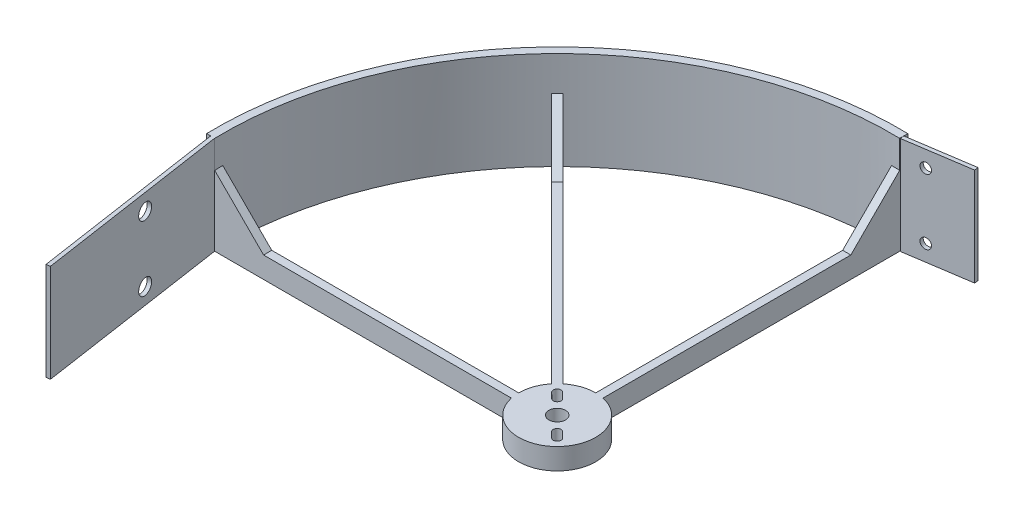
SolidWorks part; units mm, degrees
material "ABS"
ref_plane "Front Plane" through (0, 0, 0) normal (0, 0, 1) x (1, 0, 0)
ref_plane "Top Plane" through (0, 0, 0) normal (0, 1, 0) x (1, 0, 0)
ref_plane "Right Plane" through (0, 0, 0) normal (1, 0, 0) x (0, 0, -1)
sketch "Sketch1" plane through (0, 0, 0) normal (0, 1, 0) x (1, 0, 0)
  line L0 (0, 130.175) -> (0, 9.3426)
  line L1 (3.175, 9.3426) -> (3.175, 130.1363)
  line L2 (0, 0) -> (-22.0351, 22.0351) construction
  line L3 (-22.0351, 22.0351) -> (23.6345, -23.6345) construction
  line L4 (-9.3426, -3.175) -> (-130.1363, -3.175)
  line L5 (-130.175, 0) -> (-9.3426, 0)
  line L6 (3.175, 9.3426) -> (3.175, 130.1363)
  line L7 (3.175, 130.1363) -> (3.175, 133.3122)
  line L8 (-130.1363, -3.175) -> (-133.3122, -3.175)
  line L9 (-93.1633, 90.9182) -> (-10.2883, 8.0432)
  line L10 (-90.9182, 93.1633) -> (-7.1863, 9.4313)
  line L11 (0, 0) -> (-130.175, 0)
  line L12 (-130.175, 0) -> (-129.9364, 0.0546) construction
  line L13 (0, 0) -> (0, 146.05) construction
  circle A0 centre (0, 0) radius 15
  arc A1 (3.175, 130.1363) -> (-130.1363, -3.175) centre (0, 0) ccw
  arc A2 (3.175, 133.3122) -> (-133.3122, -3.175) centre (0, 0) ccw
  point P22 (0, 0)
  dimension "D1" = 30
  dimension "D2" = 133.35
  dimension "D4" = 3.175
  dimension "D3" = 3.175
  dimension "D6" = 1.5875
  dimension "D5" = 1.5875
extrude "Boss-Extrude2" add sketch "Sketch1" along normal blind 8.255 contours A0
extrude "Boss-Extrude3" add sketch "Sketch1<6>" along normal blind 8.255 contours L5 A1 L4 A0 | L6 A1 L0 A0 | A1 A0 region at (1.5882, 0, -72.5246) region at (-51.3161, 0, -51.3161) region at (-72.5246, 0, 1.5882)
sketch "Sketch1<6>" plane through (0, 0, 0) normal (0, 1, 0) x (1, 0, 0) same geometry as "Sketch1"
extrude "Boss-Extrude4" add sketch "Sketch1<7>" along normal blind 38.1 contours L7 A2 L8 A1 region at (-49.8095, 0, -122.3558)
sketch "Sketch1<7>" plane through (0, 0, 0) normal (0, 1, 0) x (1, 0, 0) same geometry as "Sketch1"
ref_plane "Plane1" through (-63.4806, 0, -63.4806) normal (0.7071, 0, 0.7071) x (0.7071, 0, -0.7071)
sketch "Sketch5" plane through (0, 8.255, 0) normal (0, 1, 0) x (1, 0, 0)
  line L0 (0, 0) -> (29.635, 0) construction
  line L1 (0, 0) -> (0, 21.5427) construction
  line L2 (0, 130.175) -> (0, 15) construction
  line L3 (0, 0) -> (29.1655, -1.7838) construction
  line L4 (21.3209, -1.304) -> (-27.7157, 1.6952) construction
  line L5 (0, 0) -> (1.3244, 21.6543) construction
  line L6 (0, 8) -> (0, 0) construction
  line L7 (0, 0) -> (37.8993, -60.1598) construction
  line L8 (0, 0) -> (-19.6346, 0) construction
  line L9 (-130.175, 0) -> (-15, 0) construction
  circle A6 centre (0, 0) radius 3.25
  point P18 (0, 0)
  dimension "D8" = 6.5
  dimension "D2" = 8
  dimension "D5" = 93.5
  dimension "D9" = 90
  dimension "D4" = 57.79
extrude "Cut-Extrude3" cut sketch "Sketch5" against normal blind 63.5
sketch "Sketch6" plane through (0, 0, 3.175) normal (0, 0, 1) x (1, 0, 0)
  line L0 (-14.6601, 0) -> (-133.3122, 0) construction
  line L1 (-130.1363, 38.1) -> (-131.7242, 38.1)
  line L2 (-130.1363, 38.1) -> (-130.1363, 0)
  line L3 (-130.1363, 0) -> (-131.7242, 0)
  line L4 (-131.7242, 38.1) -> (-131.7242, 0)
  line L5 (-130.1363, 38.1) -> (-133.3122, 38.1) construction
  point P7 (-131.7242, 38.1)
sketch "Sketch7" plane through (3.175, 0, 0) normal (1, 0, 0) x (0, 0, -1)
  line L0 (14.6601, 0) -> (133.3122, 0) construction
  line L1 (130.1363, 38.1) -> (131.7242, 38.1)
  line L2 (130.1363, 38.1) -> (130.1363, 0)
  line L3 (130.1363, 0) -> (131.7242, 0)
  line L4 (131.7242, 38.1) -> (131.7242, 0)
  line L5 (130.1363, 38.1) -> (133.3122, 38.1) construction
  line L6 (130.1363, 38.1) -> (130.1363, 8.255) construction
  point P7 (131.7242, 38.1)
ref_plane "Plane3" through (1.1225, 0, -1.1225) normal (0.7071, 0, -0.7071) x (-0.7071, 0, -0.7071)
ref_plane "Plane5" through (0, 0, 0) normal (0, 0, -1) x (-1, 0, 0)
sketch "Sketch14" plane through (0, 0, 0) normal (0, 0, -1) x (-1, 0, 0)
  line L0 (130.175, 8.255) -> (111.125, 8.255)
  line L2 (130.175, 8.255) -> (15, 8.255) construction
  line L5 (130.175, 8.255) -> (130.175, 27.305)
  line L6 (130.175, 8.255) -> (130.175, 38.1) construction
  line L7 (130.175, 27.305) -> (111.125, 8.255)
  dimension "D1" = 19.05
  dimension "D2" = 45
extrude "Boss-Extrude13" add sketch "Sketch14" against normal blind 3.175
ref_plane "Plane6" through (0, 0, 0) normal (-1, 0, 0) x (0, 0, 1)
sketch "Sketch15" plane through (0, 0, 0) normal (-1, 0, 0) x (0, 0, 1)
  line L0 (-130.175, 8.255) -> (-130.175, 27.305)
  line L1 (-130.175, 38.1) -> (-130.175, 8.255) construction
  line L2 (-130.175, 27.305) -> (-111.125, 8.255)
  line L3 (-130.175, 8.255) -> (-15, 8.255) construction
  line L5 (-111.125, 8.255) -> (-130.175, 8.255)
  dimension "D1" = 19.05
  dimension "D2" = 45
extrude "Boss-Extrude14" add sketch "Sketch15" against normal blind 3.175
sketch "Sketch16" plane through (1.1225, 0, -1.1225) normal (0.7071, 0, -0.7071) x (-0.7071, 0, -0.7071)
  line L0 (133.3403, 8.255) -> (111.1153, 8.255)
  line L2 (130.1653, 8.255) -> (14.9158, 8.255) construction
  line L4 (133.3403, 8.255) -> (133.3403, 27.305)
  line L5 (133.3403, 27.305) -> (111.1153, 8.255)
  dimension "D1" = 22.225
  dimension "D2" = 19.05
extrude "Boss-Extrude15" add sketch "Sketch16" against normal blind 3.175
sketch "Sketch17" plane through (0, 8.255, 0) normal (0, 1, 0) x (1, 0, 0)
  line L0 (4.1992, -4.1992) -> (-74.3712, 74.3712) construction
  line L1 (-5.5678, 5.5678) -> (-7.723, 7.723) construction
  line L2 (-6.6454, 4.4901) -> (-8.8007, 6.6454)
  line L3 (-4.4901, 6.6454) -> (-6.6454, 8.8007)
  line L4 (0, 0) -> (19.05, 19.05) construction
  line L5 (5.5678, -5.5678) -> (7.723, -7.723) construction
  line L6 (4.4901, -6.6454) -> (6.6454, -8.8007)
  line L7 (6.6454, -4.4901) -> (8.8007, -6.6454)
  arc A0 (-6.6454, 4.4901) -> (-4.4901, 6.6454) centre (-5.5678, 5.5678) ccw
  arc A1 (-6.6454, 8.8007) -> (-8.8007, 6.6454) centre (-7.723, 7.723) ccw
  arc A2 (4.4901, -6.6454) -> (6.6454, -4.4901) centre (5.5678, -5.5678) cw
  arc A3 (8.8007, -6.6454) -> (6.6454, -8.8007) centre (7.723, -7.723) cw
  point P3 (-6.6454, 6.6454)
  point P9 (0, 0)
  point P16 (6.6454, -6.6454)
  dimension "D1" = 7.874
  dimension "D2" = 3.048
  dimension "D3" = 3.048
extrude "Cut-Extrude6" cut sketch "Sketch17" against normal through all
ref_plane "Plane7" through (-19.405, 0, -128.3093) normal (-0.1495, 0, -0.9888) x (0, -1, 0)
sketch "Sketch20" plane through (-19.405, 0, -128.3093) normal (-0.1495, 0, -0.9888) x (0, -1, 0)
  line L0 (-38.1, -22.8367) -> (-38.1, -48.2367)
  line L1 (-38.1, -48.2367) -> (0, -48.2367)
  line L2 (0, -48.2367) -> (0, -22.8367)
  line L3 (0, -22.8367) -> (-38.1, -22.8367)
  dimension "D1" = 25.4
extrude "Boss-Extrude16" add sketch "Sketch20" against normal blind 1.524
ref_plane "Plane8" through (-129.3105, 0, 19.3256) normal (-0.989, 0, 0.1478) x (0, -1, 0)
sketch "Sketch21" plane through (-129.3105, 0, 19.3256) normal (-0.989, 0, 0.1478) x (0, -1, 0)
  line L1 (-38.1, 59.87) -> (0, 59.87)
  line L2 (-38.1, 59.87) -> (-38.1, -16.33)
  line L3 (-38.1, -16.33) -> (0, -16.33)
  line L4 (0, 59.87) -> (0, -16.33)
  dimension "D1" = 76.2
extrude "Boss-Extrude17" add sketch "Sketch21" against normal blind 1.524
sketch "Sketch23" plane through (-129.3105, 0, 19.3256) normal (-0.989, 0, 0.1478) x (0.1478, 0, 0.989)
  line L0 (-16.33, 38.1) -> (-16.33, 0) construction
  line L1 (-19.05, 19.05) -> (57.15, 19.05) construction
  line L2 (59.87, 38.1) -> (-16.33, 38.1) construction
  circle A0 centre (16.0449, 31.75) radius 3
  circle A1 centre (16.0449, 6.35) radius 3
  dimension "D2" = 6
  dimension "D1" = 32.3748
  dimension "D3" = 19.05
  dimension "D4" = 6.35
extrude "Cut-Extrude7" cut sketch "Sketch23" against normal blind 2.54
sketch "Sketch24" plane through (-19.405, 0, -128.3093) normal (-0.1495, 0, -0.9888) x (-0.9888, 0, 0.1495)
  line L0 (-22.5993, 38.1) -> (-22.5993, 0) construction
  line L1 (-44.45, 19.05) -> (-25.4, 19.05) construction
  circle A0 centre (-31.4893, 31.75) radius 1.985
  circle A1 centre (-31.4893, 6.35) radius 1.985
  dimension "D2" = 3.97
  dimension "D1" = 8.89
extrude "Cut-Extrude8" cut sketch "Sketch24" against normal blind 2.54
